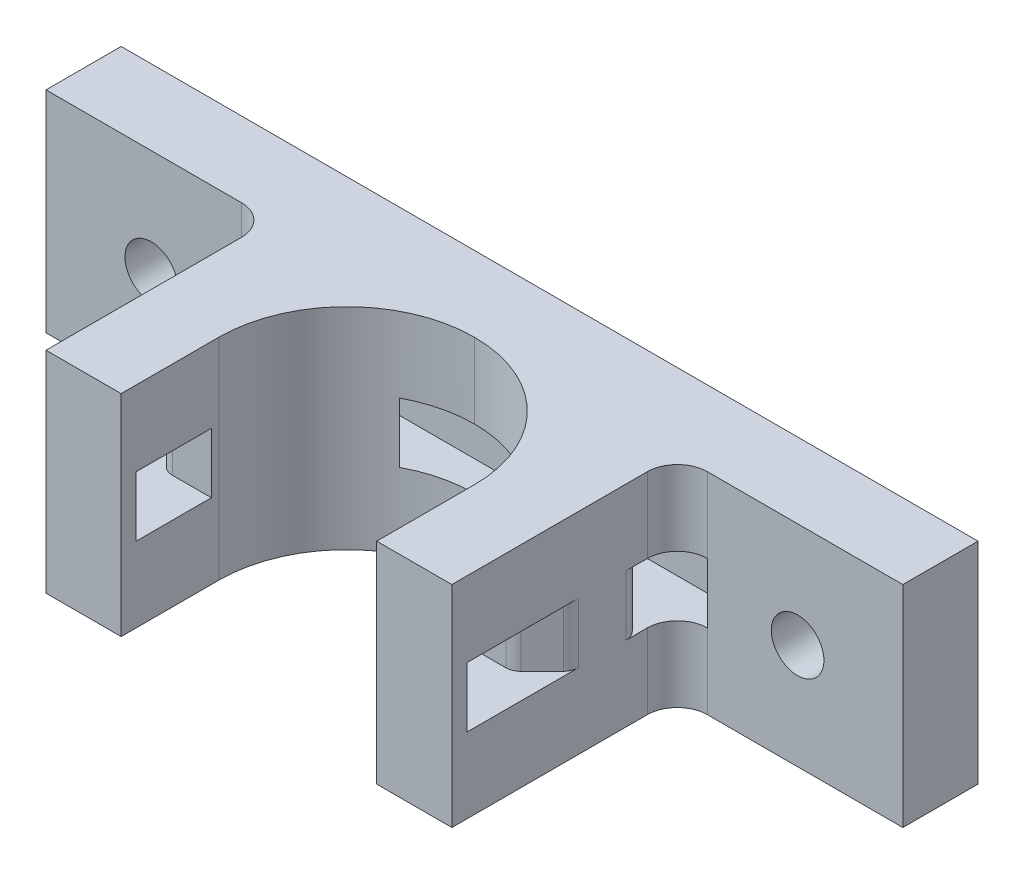
SolidWorks part; units mm, degrees
ref_plane "Plan de face" through (0, 0, 0) normal (0, 0, 1) x (1, 0, 0)
ref_plane "Plan de dessus" through (0, 0, 0) normal (0, 1, 0) x (1, 0, 0)
ref_plane "Plan de droite" through (0, 0, 0) normal (1, 0, 0) x (0, 0, -1)
sketch "Esquisse1" plane through (0, 0, 0) normal (0, 0, 1) x (1, 0, 0)
  line L1 (0, 0) -> (57, 0)
  line L2 (0, 0) -> (0, -14)
  line L3 (0, -14) -> (57, -14)
  line L4 (57, 0) -> (57, -14)
  circle A0 centre (7, -7) radius 1.75
  circle A1 centre (50, -7) radius 1.75
  point P9 (57, -7)
  point P10 (0, 0)
  point P12 (57, -9.3898)
  dimension "D2" = 3.5
  dimension "D3" = 3.5
  dimension "D1" = 43
  dimension "D4" = 7
  dimension "D5" = 7
  dimension "D6" = 7
  dimension "D7" = 7
  dimension "D8" = 7
extrude "Boss.-Extru.1" add sketch "Esquisse1" along normal blind 5
sketch "Esquisse2" plane through (0, 0, 5) normal (0, 0, 1) x (1, 0, 0)
  line L0 (57, 0) -> (0, 0) construction
  line L1 (20, 0) -> (37, 0)
  line L2 (20, 0) -> (20, -14)
  line L3 (20, -14) -> (37, -14)
  line L4 (37, 0) -> (37, -14)
  line L5 (0, -14) -> (57, -14) construction
  line L6 (0, 0) -> (0, -14) construction
  line L7 (57, -14) -> (57, 0) construction
  line L8 (15, 0) -> (15, -14)
  line L9 (42, 0) -> (42, -14)
  line M7 (0, -14) -> (57, -14)
  line M9 (57, 0) -> (0, 0)
  dimension "D1" = 20
  dimension "D2" = 20
  dimension "D3" = 17
  dimension "D4" = 5
  dimension "D5" = 5
extrude "Boss.-Extru.2" add sketch "Esquisse2" along normal blind 15 contours L8 L2 M9 M7 | L9 L4 M9 M7 region at (17.5, -7, 5) region at (39.5, -7, 5)
fillet "Congé1" radius 8.5 2 edges at (20, -7, 5) (37, -7, 5)
sketch "Esquisse3" plane through (15, 0, 0) normal (-1, 0, 0) x (0, 0, 1)
  line L0 (20, 0) -> (20, -14) construction
  line L1 (19, -5) -> (14, -5)
  line L2 (19, -5) -> (19, -9)
  line L3 (19, -9) -> (14, -9)
  line L4 (14, -5) -> (14, -9)
  line L5 (0, 0) -> (0, -14) construction
  line L6 (6, -5) -> (3, -5)
  line L7 (6, -5) -> (6, -9)
  line L8 (6, -9) -> (3, -9)
  line L9 (3, -5) -> (3, -9)
  line L10 (20, 0) -> (5, 0) construction
  point P4 (19, -7)
  point P7 (20, -7)
  point P14 (6, -7)
  dimension "D1" = 2
  dimension "D2" = 5
  dimension "D3" = 1
  dimension "D4" = 0
  dimension "D5" = 3
  dimension "D6" = 3
  dimension "D7" = 7
  dimension "D8" = 4
extrude "Enlèv. mat.-Extru.1" cut sketch "Esquisse3" along direction (1, 0, 0) on the side against the normal up to surface (27 mm away) up to face at (42, -7, 12.5)
chamfer "Chanfrein1" distance 2 angle 45 6 edges at (42, -7, 5) (15, -7, 5) (42, -7, 14) (15, -7, 14) (15, -7, 6) (42, -7, 6)
fillet "Congé2" radius 1 8 edges at (17, -7, 6) (15, -7, 8) (15, -7, 12) (17, -7, 14) (40, -7, 14) (40, -7, 6) (42, -7, 12) (42, -7, 8)
sketch "Esquisse6" plane through (0, -14, 0) normal (0, -1, 0) x (1, 0, 0)
  line L0 (0, 0.75) -> (57, 0.75) construction
  line L1 (0, 5) -> (0, 0) construction
  line L2 (57, 5) -> (57, 0) construction
  line L3 (0, 0) -> (57, 0) construction
  text T0 "GUIGUR.COM" font "Century Gothic" height 3.5
  dimension "D1" = 0.75
extrude "Boss.-Extru.3" add sketch "Esquisse6" along normal blind 0.5
fillet "Congé3" radius 2 4 edges at (42, -2.5, 5) (42, -11.5, 5) (15, -2.5, 5) (15, -11.5, 5)
